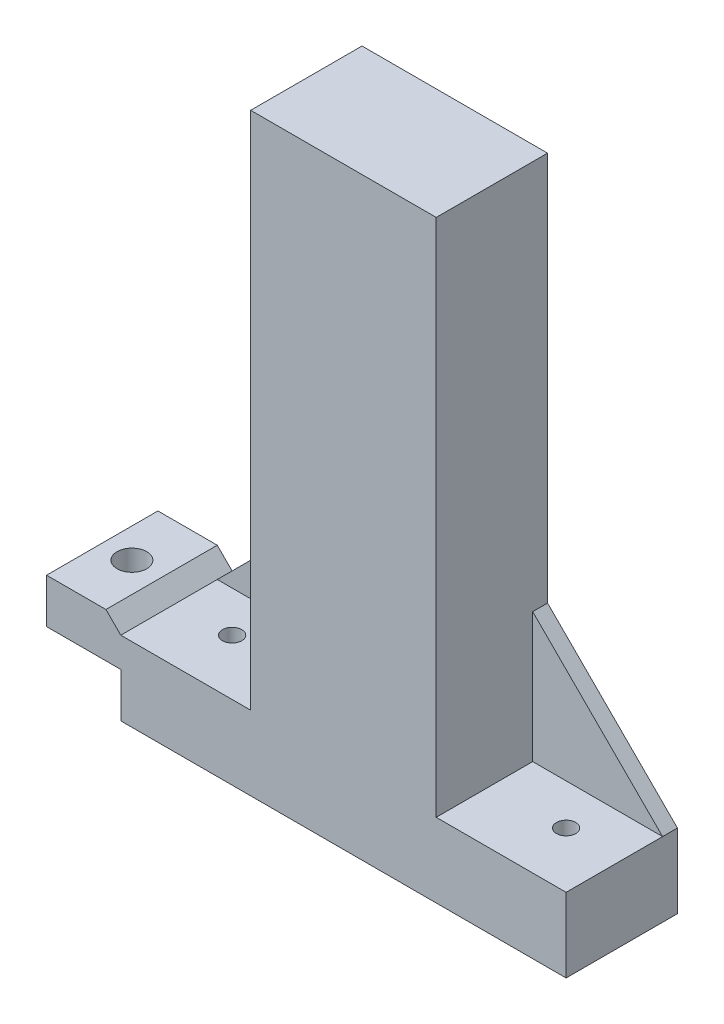
SolidWorks part; units mm, degrees
ref_plane "前基準面" through (0, 0, 0) normal (0, 0, 1) x (1, 0, 0)
ref_plane "上基準面" through (0, 0, 0) normal (0, 1, 0) x (1, 0, 0)
ref_plane "右基準面" through (0, 0, 0) normal (1, 0, 0) x (0, 0, -1)
sketch "草圖2" plane through (0, 0, 0) normal (0, 1, 0) x (1, 0, 0)
  line L5 (-30, 7.5) -> (30, 7.5)
  line L6 (-30, 7.5) -> (-30, -7.5)
  line L7 (-30, -7.5) -> (30, -7.5)
  line L8 (30, 7.5) -> (30, -7.5)
  line L9 (0, -7.5) -> (0, 7.5) construction
  line L10 (-30, 0) -> (30, 0) construction
  circle A4 centre (-22.5, 0) radius 1.3
  circle A5 centre (22.5, 0) radius 1.3
  point P0 (0, 0)
  dimension "D3" = 45
  dimension "D2" = 2.6
  dimension "D1" = 60
  dimension "D4" = 15
extrude "填料-伸長1" add sketch "草圖2" along normal blind 10
sketch "草圖3" plane through (0, 10, 0) normal (0, 1, 0) x (1, 0, 0)
  line L0 (-30, -7.5) -> (30, -7.5) construction
  line L1 (-12.5, 7.5) -> (12.5, 7.5)
  line L2 (-12.5, 7.5) -> (-12.5, -7.5)
  line L3 (-12.5, -7.5) -> (12.5, -7.5)
  line L4 (12.5, 7.5) -> (12.5, -7.5)
  line L5 (0, -7.5) -> (0, 7.5) construction
  line L6 (-12.5, 0) -> (12.5, 0) construction
  point P0 (0, 0)
  point P6 (-22.5, 0)
  point P7 (22.5, 0)
  dimension "D1" = 25
  dimension "D2" = 10
extrude "填料-伸長2" add sketch "草圖3" along normal blind 70
sketch "草圖5" plane through (0, 0, -7.5) normal (0, 0, -1) x (-1, 0, 0)
  line L0 (-30, 10) -> (-12.5, 27.5)
  line L1 (-12.5, 80) -> (-12.5, 10) construction
  line L2 (-12.5, 27.5) -> (-12.5, 10)
  line L3 (-12.5, 10) -> (-30, 10)
  line L4 (0, 0) -> (0, 43.0538) construction
  line L5 (-30, 0) -> (30, 0) construction
  line L6 (12.5, 27.5) -> (12.5, 10)
  line L7 (30, 10) -> (12.5, 27.5)
  line L8 (12.5, 10) -> (30, 10)
  dimension "D1" = 45
extrude "填料-伸長3" add sketch "草圖5" against normal blind 2
sketch "草圖6" plane through (0, 0, 7.5) normal (0, 0, 1) x (1, 0, 0)
  line L0 (-30, 6) -> (-40, 6)
  line L2 (-30, 12) -> (-30, 6)
  line L3 (-30, 12) -> (-40, 12)
  line L4 (-40, 12) -> (-40, 6)
  line L5 (-30, 0) -> (30, 0) construction
  line L6 (-30, 10) -> (-30, 0) construction
  point P0 (0, 0)
  dimension "D1" = 10
  dimension "D2" = 6
  dimension "D3" = 6
extrude "填料-伸長4" add sketch "草圖6" against normal up to surface (15 mm away) up to face at (0, 29.375, -7.5)
sketch "草圖7" plane through (0, 10, 0) normal (0, 1, 0) x (1, 0, 0)
  line L3 (-40, 7.5) -> (-40, -7.5) construction
  circle A0 centre (-36, 0) radius 2
  dimension "D1" = 4
  dimension "D2" = 4
extrude "除料-伸長1" cut sketch "草圖7" against normal through all both and the other way through all
chamfer "導角1" distance 2 angle 45 1 edges at (-30, 12, 0)
